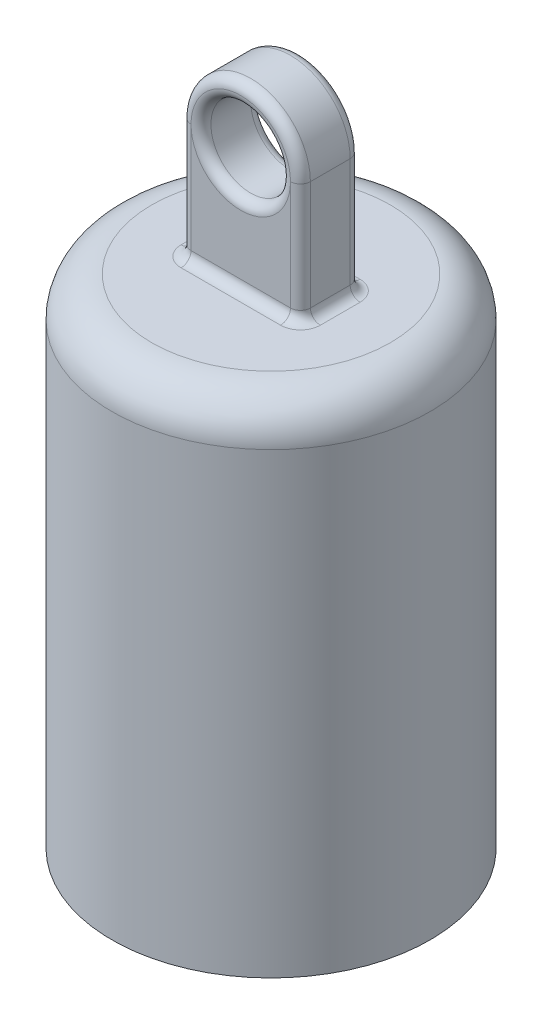
SolidWorks part; units mm, degrees
ref_plane "前视基准面" through (0, 0, 0) normal (0, 0, 1) x (1, 0, 0)
ref_plane "上视基准面" through (0, 0, 0) normal (0, 1, 0) x (1, 0, 0)
ref_plane "右视基准面" through (0, 0, 0) normal (1, 0, 0) x (0, 0, -1)
sketch "草图1" plane through (0, 0, 0) normal (0, 0, 1) x (1, 0, 0)
  line L1 (0, 0) -> (6, 0)
  line L2 (0, 0) -> (0, 6)
  line L4 (6, 0) -> (6, 6)
  arc A0 (6, 6) -> (0, 6) centre (3, 6) ccw
  circle A1 centre (3, 6) radius 2
extrude "凸台-拉伸1" add sketch "草图1" along normal mid plane 3
sketch "草图2" plane through (0, 0, 0) normal (0, -1, 0) x (1, 0, 0)
  circle A0 centre (3.0228, 0) radius 8
extrude "凸台-拉伸2" add sketch "草图2" along normal blind 25
sketch "草图3" plane through (0, -25, 0) normal (0, -1, 0) x (1, 0, 0)
  circle A0 centre (2.9948, 0) radius 1.5
extrude "切除-拉伸1" cut sketch "草图3" against normal blind 2
sketch "草图4" plane through (0, -23, 0) normal (0, -1, 0) x (1, 0, 0)
  circle A0 centre (2.9948, 0) radius 6
  circle A1 centre (2.9948, 0) radius 1.5 construction
  dimension "D1" = 4.5
extrude "切除-拉伸2" cut sketch "草图4" against normal blind 20
fillet "圆角5" radius 0.5 12 edges at (0, 0, 0) (6, 0, 0) (5, 6, 1.5) (3, 9, 1.5) (6, 3, 1.5) (3, 0, 1.5) (0, 3, 1.5) (5, 6, -1.5) (3, 0, -1.5) (6, 3, -1.5) (3, 9, -1.5) (0, 3, -1.5)
fillet "圆角6" radius 2 1 edges at (3.0228, 0, -8)
